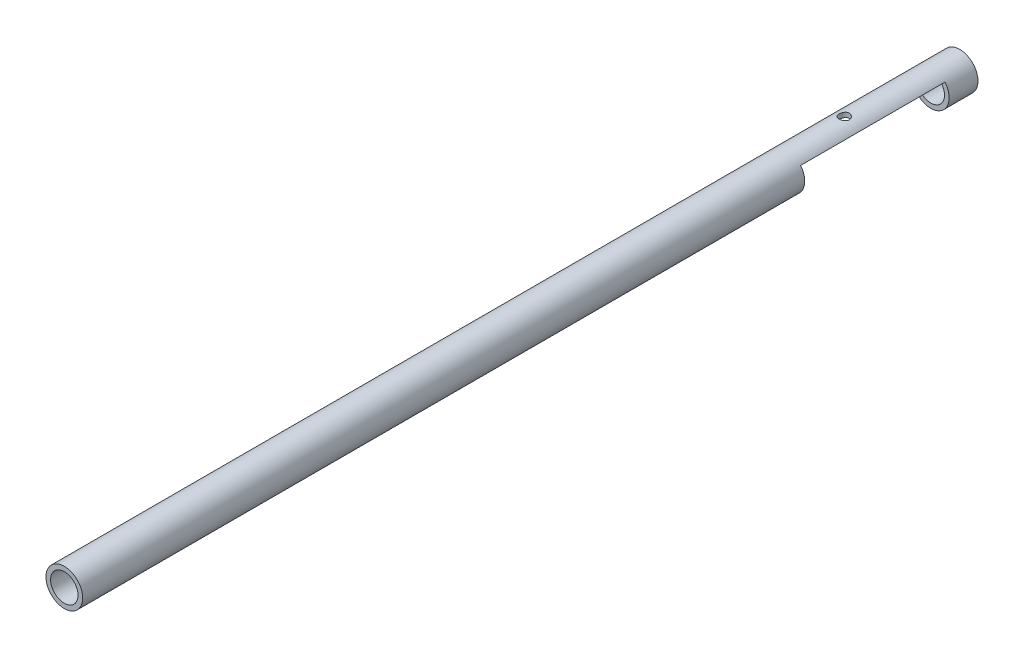
SolidWorks part; units mm, degrees
ref_plane "Front Plane" through (0, 0, 0) normal (0, 0, 1) x (1, 0, 0)
ref_plane "Top Plane" through (0, 0, 0) normal (0, 1, 0) x (1, 0, 0)
ref_plane "Right Plane" through (0, 0, 0) normal (1, 0, 0) x (0, 0, -1)
sketch "Sketch1" plane through (0, 0, 0) normal (0, 0, 1) x (1, 0, 0)
  circle A0 centre (0, 0) radius 2.375
  circle A1 centre (0, 0) radius 3.175
  dimension "D1" = 4.75
  dimension "D2" = 6.35
extrude "Boss-Extrude1" add sketch "Sketch1" along normal blind 155
sketch "Sketch2" plane through (0, 0, 0) normal (0, 1, 0) x (1, 0, 0)
  line L1 (-5.5281, -30) -> (7.5019, -30)
  line L2 (-5.5281, -30) -> (-5.5281, -5)
  line L3 (-5.5281, -5) -> (7.5019, -5)
  line L4 (7.5019, -30) -> (7.5019, -5)
  dimension "D1" = 5
  dimension "D2" = 25
extrude "Cut-Extrude1" cut sketch "Sketch2" against normal blind 5 and the other way blind 2
sketch "Sketch3" plane through (0, 2, 0) normal (0, -1, 0) x (-1, 0, 0)
  line L0 (2.375, -30) -> (-2.375, -30) construction
  circle A0 centre (0, -20) radius 0.889
  point P2 (0, -30)
  dimension "D1" = 1.778
  dimension "D2" = 10
extrude "2-56 hole" cut sketch "Sketch3" against normal blind 3
